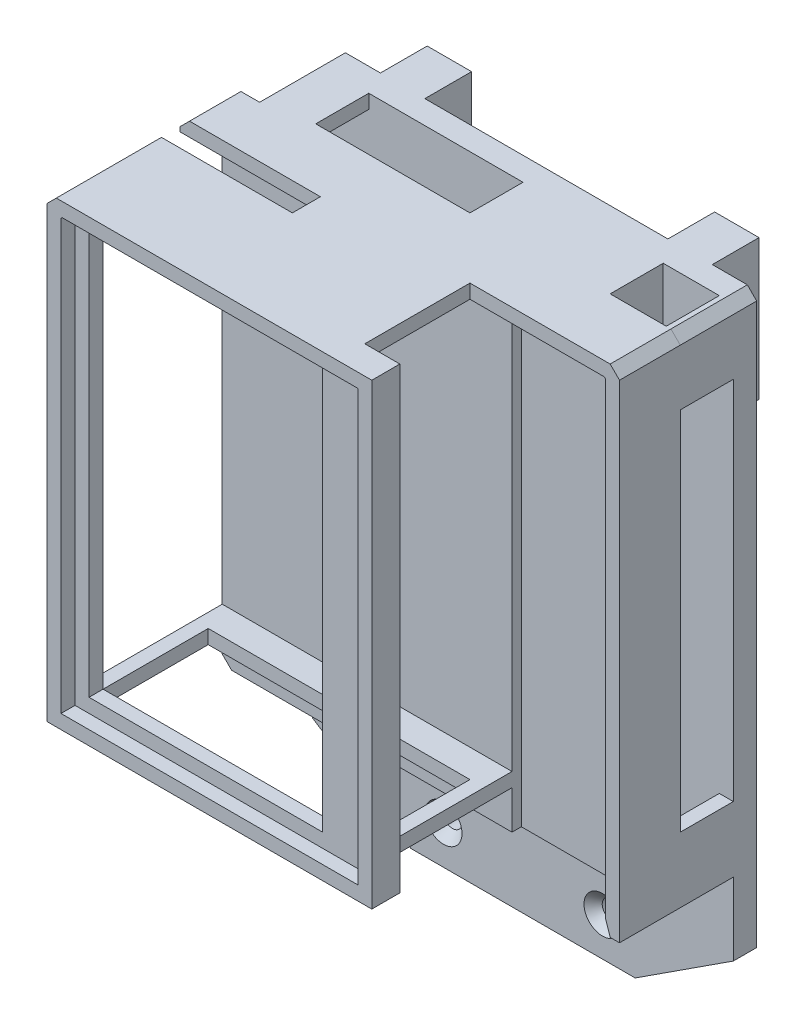
SolidWorks part; units mm, degrees
note: The reader was unsure of these and kept them because the rebuilt part matched: shared geometry of "Sketch14<2>".
ref_plane "Front Plane" through (0, 0, 0) normal (0, 0, 1) x (1, 0, 0)
ref_plane "Top Plane" through (0, 0, 0) normal (0, 1, 0) x (1, 0, 0)
ref_plane "Right Plane" through (0, 0, 0) normal (1, 0, 0) x (0, 0, -1)
sketch "Sketch2" plane through (0, 0, 0) normal (0, 0, 1) x (1, 0, 0)
  line L0 (-45, 122) -> (-45, 0.1976)
  line L1 (-24, -13.44) -> (24, -13.44)
  line L2 (45, 0.1976) -> (45, 122)
  line L3 (45, 122) -> (-45, 122)
  line L4 (-45, 0.1976) -> (-24, -13.44)
  line L5 (24, -13.44) -> (45, 0.1976)
  line L6 (52.1567, -47.9756) -> (61.3959, -41.9756) construction
  line L7 (-58.6041, -41.9756) -> (-49.3649, -47.9756) construction
  dimension "D1" = 48
  dimension "D2" = 135.44
extrude "Boss-Extrude1" add sketch "Sketch2" along normal blind 5
chamfer "Chamfer1" distance 2 2 edges at (-45, 122, 2.5) (45, 122, 2.5)
sketch "Sketch4" plane through (0, 0, 5) normal (0, 0, 1) x (1, 0, 0)
  line L0 (-45, 120) -> (-43, 122)
  line L1 (-43, 122) -> (-33, 122)
  line L2 (43, 122) -> (-43, 122) construction
  line L3 (-33, 122) -> (-33, 119)
  line L4 (-33, 119) -> (-41.7574, 119)
  line L5 (-41.7574, 119) -> (-42, 118.7574)
  line L9 (-45, 118.7574) -> (-45, 120)
  line L10 (-42, 118.7574) -> (-45, 118.7574)
  line L11 (-45, 15.7574) -> (-33, 15.7574)
  line L12 (-45, 120) -> (-45, 0.1976) construction
  line L13 (-33, 15.7574) -> (-33, 18.7574)
  line L14 (-33, 18.7574) -> (-45, 18.7574)
  line L15 (-45, 18.7574) -> (-45, 15.7574)
  line L16 (0, 122) -> (30, 122)
  line L17 (30, 122) -> (30, 108)
  line L18 (30, 108) -> (27, 108)
  line L19 (27, 108) -> (27, 119)
  line L20 (27, 119) -> (0, 119)
  line L21 (0, 119) -> (0, 122)
  line L22 (0, 15.7574) -> (30, 15.7574)
  line L23 (30, 15.7574) -> (30, 29.7574)
  line L24 (30, 29.7574) -> (27, 29.7574)
  line L25 (27, 29.7574) -> (27, 18.7574)
  line L26 (27, 18.7574) -> (0, 18.7574)
  line L27 (0, 18.7574) -> (0, 15.7574)
  dimension "D1" = 100
  dimension "D2" = 3
  dimension "D3" = 3
  dimension "D4" = 3
  dimension "D5" = 3
  dimension "D6" = 3
  dimension "D7" = 3
  dimension "D8" = 72
  dimension "D9" = 14
  dimension "D10" = 30
  dimension "D11" = 12
extrude "Boss-Extrude2" add sketch "Sketch4" along normal blind 11.35
sketch "Sketch5" plane through (0, 0, 16.35) normal (0, 0, 1) x (1, 0, 0)
  line L0 (-33, 122) -> (-43, 122) construction
  line L1 (45, 15.7574) -> (-45, 15.7574)
  line L2 (45, 15.7574) -> (45, 122)
  line L3 (45, 122) -> (-43, 122)
  line L4 (-45, 15.7574) -> (-45, 120)
  line L6 (-45, 118.7574) -> (-45, 18.7574) construction
  line L7 (-43, 122) -> (-45, 120)
  line L8 (45, 0.1976) -> (45, 120) construction
  line L9 (0, 15.7574) -> (30, 15.7574) construction
  point P1 (-45, 122)
extrude "Boss-Extrude3" add sketch "Sketch5" along normal blind 4 contours L2 L1 L4 L7 L3
sketch "Sketch6" plane through (0, 0, 5) normal (0, 0, 1) x (1, 0, 0)
  line L0 (38, 122) -> (43, 122)
  line L1 (43, 122) -> (30, 122) construction
  line L2 (43, 122) -> (45, 120)
  line L3 (45, 120) -> (45, 115)
  line L4 (45, 0.1976) -> (45, 120) construction
  line L5 (45, 115) -> (42, 115)
  line L6 (42, 115) -> (42, 118.7574)
  line L7 (42, 118.7574) -> (41.7574, 119)
  line L8 (41.7574, 119) -> (38, 119)
  line L9 (38, 119) -> (38, 122)
  line L10 (45, 15.7574) -> (39, 15.7574)
  line L11 (39, 15.7574) -> (39, 18.7574)
  line L12 (39, 18.7574) -> (42, 18.7574)
  line L13 (42, 18.7574) -> (42, 21.7574)
  line L14 (42, 21.7574) -> (45, 21.7574)
  line L15 (45, 21.7574) -> (45, 15.7574)
  line L16 (45, 15.7574) -> (-45, 15.7574) construction
  dimension "D1" = 3
  dimension "D2" = 3
  dimension "D3" = 3
  dimension "D4" = 5
  dimension "D5" = 5
  dimension "D6" = 3
  dimension "D7" = 3
  dimension "D8" = 6
  dimension "D9" = 6
extrude "Boss-Extrude4" add sketch "Sketch6" along normal up to surface (11.35 mm away) up to face at (0.5565, 73.4131, 16.35)
chamfer "Chamfer2" distance 2 1 edges at (45, 122, 18.35)
sketch "Sketch8" plane through (0, 0, 20.35) normal (0, 0, 1) x (1, 0, 0)
  line L0 (-37, 15.7574) -> (-37, 122)
  line L1 (45, 15.7574) -> (-45, 15.7574) construction
  line L2 (43, 122) -> (-43, 122) construction
  line L3 (-37, 122) -> (-43, 122)
  line L4 (-43, 122) -> (-45, 120)
  line L5 (-45, 120) -> (-45, 15.7574)
  line L6 (-45, 15.7574) -> (-37, 15.7574)
  line M8 (43, 122) -> (-43, 122)
  line M9 (-43, 122) -> (-45, 120)
  line M10 (-45, 120) -> (-45, 15.7574)
  line M11 (-45, 15.7574) -> (45, 15.7574)
  dimension "D1" = 8
extrude "Cut-Extrude2" cut sketch "Sketch8" against normal blind 2 contours L0 M11 M8 M9 M10
sketch "Sketch9" plane through (0, 0, 20.35) normal (0, 0, 1) x (1, 0, 0)
  line L0 (-37, 18.7574) -> (42, 18.7574)
  line L1 (42, 18.7574) -> (42, 118.7574)
  line L2 (42, 118.7574) -> (41.7574, 119)
  line L3 (41.7574, 119) -> (-37, 119)
  line L4 (-37, 18.7574) -> (-37, 15.7574)
  line L5 (43, 122) -> (-37, 122)
  line L6 (-37, 122) -> (-37, 15.7574)
  line L7 (-37, 15.7574) -> (45, 15.7574)
  line L8 (45, 15.7574) -> (45, 120)
  line L9 (45, 120) -> (43, 122)
  line L10 (43, 122) -> (-37, 122)
  line L12 (-37, 15.7574) -> (45, 15.7574)
  line L13 (45, 15.7574) -> (45, 120)
  line L14 (45, 120) -> (43, 122)
  line L15 (-37, 122) -> (-37, 119)
  dimension "D1" = 0
  dimension "D2" = 3
extrude "Boss-Extrude5" add sketch "Sketch9" along normal blind 9 contours L10 L15 L3 L2 L1 L0 L4 L12 L13 L14
sketch "Sketch10" plane through (-37, 0, 0) normal (-1, 0, 0) x (0, 0, 1)
  line L8 (18.35, 15.7574) -> (29.35, 15.7574)
  line L9 (29.35, 15.7574) -> (29.35, 18.7574)
  line L10 (29.35, 18.7574) -> (20.35, 18.7574)
  line L11 (20.35, 18.7574) -> (20.35, 119)
  line L12 (20.35, 119) -> (29.35, 119)
  line L13 (29.35, 119) -> (29.35, 122)
  line L14 (29.35, 122) -> (18.35, 122)
  line L15 (18.35, 122) -> (18.35, 15.7574)
  line L16 (18.35, 15.7574) -> (29.35, 15.7574)
  line L17 (29.35, 15.7574) -> (29.35, 18.7574)
  line L18 (29.35, 18.7574) -> (20.35, 18.7574)
  line L19 (20.35, 18.7574) -> (20.35, 119)
  line L20 (20.35, 119) -> (29.35, 119)
  line L21 (29.35, 119) -> (29.35, 122)
  line L22 (29.35, 122) -> (18.35, 122)
  line L23 (18.35, 122) -> (18.35, 15.7574)
  dimension "D1" = 0
extrude "Boss-Extrude6" add sketch "Sketch10" along normal blind 12
sketch "Sketch11" plane through (0, 0, 20.35) normal (0, 0, 1) x (1, 0, 0)
  line L0 (-49, 18.7574) -> (-49, 119)
  line L1 (-49, 119) -> (-46, 119)
  line L2 (41.7574, 119) -> (-49, 119) construction
  line L3 (-46, 119) -> (-46, 18.7574)
  line L4 (-49, 18.7574) -> (42, 18.7574) construction
  line L5 (-46, 18.7574) -> (-49, 18.7574)
  dimension "D1" = 3
extrude "Boss-Extrude7" add sketch "Sketch11" along normal up to surface (9 mm away) up to face at (6.2757, 78.9787, 29.35)
chamfer "Chamfer3" distance 2 2 edges at (-49, 15.7574, 23.85) (-49, 122, 23.85)
sketch "Sketch12" plane through (0, 18.7574, 0) normal (0, 1, 0) x (1, 0, 0)
  line L0 (-46, -20.35) -> (42, -20.35) construction
  line L1 (38, -25.35) -> (17, -25.35)
  line L2 (38, -25.35) -> (38, -20.35)
  line L3 (38, -20.35) -> (17, -20.35)
  line L4 (17, -25.35) -> (17, -20.35)
  dimension "D1" = 21
  dimension "D2" = 4
extrude "Cut-Extrude3" cut sketch "Sketch12" against normal blind 9
chamfer "Chamfer5" distance 2.33 angle 65 2 edges at (38, 18.7574, 22.85) (17, 18.7574, 22.85)
sketch "Sketch13" plane through (0, 122, 0) normal (0, 1, 0) x (1, 0, 0)
  line L1 (30, -16.35) -> (42, -16.35)
  line L2 (30, -16.35) -> (30, -5)
  line L3 (30, -5) -> (42, -5)
  line L4 (42, -16.35) -> (42, -5)
extrude "Cut-Extrude4" cut sketch "Sketch13" against normal blind 117
sketch "Sketch14" plane through (0, 115, 0) normal (0, -1, 0) x (1, 0, 0)
  line L4 (45, 5) -> (45, 16.35)
  line L5 (45, 16.35) -> (42, 16.35)
  line L6 (42, 16.35) -> (42, 5)
  line L7 (42, 5) -> (45, 5)
  line L8 (45, 5) -> (45, 16.35)
  line L9 (45, 16.35) -> (42, 16.35)
  line L10 (42, 16.35) -> (42, 5)
  line L11 (42, 5) -> (45, 5)
  dimension "D1" = 0
extrude "Boss-Extrude8" add sketch "Sketch14" along normal up to surface (7 mm away) up to face at (28.5, 108, 10.675)
extrude "Boss-Extrude9" add sketch "Sketch14<2>" along normal up to surface (8 mm away) from surface
sketch "Sketch14<2>" plane through (0, 115, 0) normal (0, -1, 0) x (1, 0, 0) same geometry as "Sketch14"
sketch "Sketch15" plane through (-49, 0, 0) normal (-1, 0, 0) x (0, 0, 1)
  line L0 (29.35, 17.7574) -> (29.35, 120) construction
  line L1 (29.35, 119) -> (20.35, 119)
  line L2 (29.35, 119) -> (29.35, 27)
  line L3 (29.35, 27) -> (20.35, 27)
  line L4 (20.35, 119) -> (20.35, 27)
  line L6 (20.35, 18.7574) -> (20.35, 119) construction
  dimension "D1" = 92
extrude "Cut-Extrude5" cut sketch "Sketch15" against normal blind 10
sketch "Sketch16" plane through (0, 0, 29.35) normal (0, 0, 1) x (1, 0, 0)
  line L0 (13, 122) -> (13, 119)
  line L1 (-49, 27) -> (13, 27)
  line L2 (13, 27) -> (13, 24)
  line L3 (13, 24) -> (-49, 24)
  line L5 (-49, 24) -> (-49, 27)
  line L6 (-46, 27) -> (-49, 27) construction
  line L7 (-49, 17.7574) -> (-49, 27) construction
  line L14 (-46, 27) -> (-49, 27)
  line L15 (-49, 27) -> (-49, 17.7574)
  line L16 (-49, 17.7574) -> (-47, 15.7574)
  line L17 (-47, 15.7574) -> (45, 15.7574)
  line L18 (45, 15.7574) -> (45, 120)
  line L19 (45, 120) -> (43, 122)
  line L20 (43, 122) -> (-47, 122)
  line L21 (-47, 122) -> (-49, 120)
  line L22 (-49, 120) -> (-49, 119)
  line L23 (-49, 119) -> (41.7574, 119)
  line L24 (41.7574, 119) -> (42, 118.7574)
  line L25 (42, 118.7574) -> (42, 18.7574)
  line L26 (42, 18.7574) -> (-46, 18.7574)
  line L27 (-46, 18.7574) -> (-46, 27)
  line L34 (13, 122) -> (-47, 122)
  line L35 (-47, 122) -> (-49, 120)
  line L36 (-49, 120) -> (-49, 119)
  line L37 (-49, 119) -> (13, 119)
  dimension "D2" = 62
  dimension "D3" = 3
  dimension "D1" = 0
extrude "Boss-Extrude10" add sketch "Sketch16" along normal blind 31.5 from surface at -9 starting at face at (4.8134, 44.2445, 20.35)
sketch "Sketch17" plane through (0, 0, 51.85) normal (0, 0, 1) x (1, 0, 0)
  line L0 (-49, 119) -> (-49, 27)
  line L1 (13, 27) -> (13, 119)
  line L4 (-49, 24) -> (13, 24)
  line L5 (-47, 122) -> (-49, 120)
  line L6 (-49, 120) -> (-49, 119)
  line L7 (-49, 119) -> (13, 119)
  line L8 (13, 119) -> (13, 122)
  line L9 (13, 122) -> (-47, 122)
  line L10 (-47, 122) -> (-49, 120)
  line L11 (-49, 120) -> (-49, 119)
  line L13 (13, 119) -> (13, 122)
  line L14 (13, 122) -> (-47, 122)
  line L15 (13, 24) -> (13, 27)
  line L16 (13, 27) -> (-49, 27)
  line L17 (-49, 27) -> (-49, 24)
  line L18 (-49, 24) -> (13, 24)
  line L19 (13, 24) -> (13, 27)
  line L21 (-49, 27) -> (-49, 24)
  dimension "D1" = 0
  dimension "D2" = 0
extrude "Boss-Extrude12" add sketch "Sketch17" along normal blind 6
sketch "Sketch18" plane through (0, 0, 57.85) normal (0, 0, 1) x (1, 0, 0)
  line L10 (7, 116) -> (-43, 116)
  line L11 (-43, 116) -> (-43, 30)
  line L12 (-43, 30) -> (7, 30)
  line L13 (7, 30) -> (7, 116)
  line L14 (7, 116) -> (-43, 116)
  line L15 (-43, 116) -> (-43, 30)
  line L16 (-43, 30) -> (7, 30)
  line L17 (7, 30) -> (7, 116)
  dimension "D1" = 6
extrude "Cut-Extrude6" cut sketch "Sketch18" against normal blind 6
sketch "Sketch19" plane through (0, 0, 57.85) normal (0, 0, 1) x (1, 0, 0)
  line L10 (10, 119) -> (-45.7574, 119)
  line L11 (-45.7574, 119) -> (-46, 118.7574)
  line L12 (-46, 118.7574) -> (-46, 27)
  line L13 (-46, 27) -> (10, 27)
  line L14 (10, 27) -> (10, 119)
  line L15 (10, 119) -> (-45.7574, 119)
  line L16 (-45.7574, 119) -> (-46, 118.7574)
  line L17 (-46, 118.7574) -> (-46, 27)
  line L18 (-46, 27) -> (10, 27)
  line L19 (10, 27) -> (10, 119)
  dimension "D1" = 3
extrude "Cut-Extrude7" cut sketch "Sketch19" against normal blind 3
sketch "Sketch20" plane through (13, 0, 0) normal (1, 0, 0) x (0, 0, -1)
  line L0 (-57.85, 122) -> (-29.35, 122) construction
  line L1 (-57.85, 24) -> (-51.85, 24)
  line L2 (-57.85, 24) -> (-57.85, 122)
  line L3 (-57.85, 122) -> (-51.85, 122)
  line L4 (-51.85, 24) -> (-51.85, 122)
extrude "Cut-Extrude8" cut sketch "Sketch20" against normal blind 3
sketch "Sketch21" plane through (10, 0, 0) normal (1, 0, 0) x (0, 0, -1)
  line L10 (-57.85, 27) -> (-57.85, 24)
  line L11 (-57.85, 24) -> (-51.85, 24)
  line L12 (-51.85, 24) -> (-51.85, 27)
  line L13 (-51.85, 27) -> (-51.85, 119)
  line L14 (-51.85, 119) -> (-51.85, 122)
  line L15 (-51.85, 122) -> (-57.85, 122)
  line L16 (-57.85, 122) -> (-57.85, 119)
  line L17 (-57.85, 119) -> (-54.85, 119)
  line L18 (-54.85, 119) -> (-54.85, 27)
  line L19 (-54.85, 27) -> (-57.85, 27)
  line L20 (-57.85, 27) -> (-57.85, 24)
  line L21 (-57.85, 24) -> (-51.85, 24)
  line L22 (-51.85, 24) -> (-51.85, 27)
  line L23 (-51.85, 27) -> (-51.85, 119)
  line L24 (-51.85, 119) -> (-51.85, 122)
  line L25 (-51.85, 122) -> (-57.85, 122)
  line L26 (-57.85, 122) -> (-57.85, 119)
  line L27 (-57.85, 119) -> (-54.85, 119)
  line L28 (-54.85, 119) -> (-54.85, 27)
  line L29 (-54.85, 27) -> (-57.85, 27)
  dimension "D1" = 0
extrude "Boss-Extrude13" add sketch "Sketch21" along normal blind 10.5
sketch "Sketch22" plane through (0, 0, 54.85) normal (0, 0, 1) x (1, 0, 0)
  line L0 (20.5, 119) -> (20.5, 27)
  line L1 (20.5, 27) -> (17.5, 27)
  line L2 (17.5, 27) -> (17.5, 119)
  line L3 (20.5, 119) -> (-45.7574, 119) construction
  line L4 (17.5, 119) -> (20.5, 119)
  line L5 (-46, 27) -> (20.5, 27) construction
  dimension "D1" = 3
extrude "Boss-Extrude14" add sketch "Sketch22" along normal blind 3
sketch "Sketch23" plane through (0, 0, 20.35) normal (0, 0, 1) x (1, 0, 0)
  line L0 (13, 15.7574) -> (13, 119)
  line L1 (13, 119) -> (41.7574, 119)
  line L2 (41.7574, 119) -> (13, 119) construction
  line L3 (41.7574, 119) -> (-49, 119) construction
  line L4 (41.7574, 119) -> (42, 118.7574)
  line L5 (42, 118.7574) -> (41.7574, 119) construction
  line L6 (42, 118.7574) -> (42, 15.7574)
  line L7 (13, 15.7574) -> (42, 15.7574)
  line L8 (38, 15.7574) -> (17, 15.7574) construction
  line L10 (42, 18.2926) -> (42, 118.7574) construction
extrude "Cut-Extrude9" cut sketch "Sketch23" along normal blind 10 from offset 2 offset against normal yes
sketch "Sketch24" plane through (0, 0, 29.35) normal (0, 0, 1) x (1, 0, 0)
  line L0 (42, 18.7574) -> (43, 15.7574)
  line L7 (-47, 15.7574) -> (45, 15.7574)
  line L8 (13, 122) -> (13, 119)
  line L9 (42, 18.7574) -> (-46, 18.7574)
  line L10 (-46, 18.7574) -> (-46, 24)
  line L11 (-46, 24) -> (-49, 24)
  line L12 (-49, 24) -> (-49, 17.7574)
  line L13 (-49, 17.7574) -> (-47, 15.7574)
  line L14 (-47, 15.7574) -> (45, 15.7574)
  line L15 (13, 122) -> (13, 119)
  line L16 (42, 18.7574) -> (-46, 18.7574)
  line L17 (-46, 18.7574) -> (-46, 24)
  line L18 (-46, 24) -> (-49, 24)
  line L19 (-49, 24) -> (-49, 17.7574)
  line L20 (-49, 17.7574) -> (-47, 15.7574)
  line L27 (13, 119) -> (41.7574, 119)
  line L28 (13, 119) -> (41.7574, 119)
  line L29 (41.7574, 119) -> (42, 118.7574)
  line L30 (41.7574, 119) -> (42, 118.7574)
  line L31 (42, 118.7574) -> (42, 18.7574)
  line L32 (42, 118.7574) -> (42, 18.7574)
  line L33 (45, 15.7574) -> (45, 120)
  line L34 (45, 15.7574) -> (45, 120)
  line L35 (45, 120) -> (43, 122)
  line L36 (45, 120) -> (43, 122)
  line L37 (43, 122) -> (13, 122)
  line L38 (43, 122) -> (13, 122)
  line M8 (-47, 15.7574) -> (45, 15.7574)
  line M10 (42, 18.7574) -> (-46, 18.7574)
  line M11 (-46, 18.7574) -> (-46, 24)
  line M12 (-46, 24) -> (-49, 24)
  line M13 (-49, 24) -> (-49, 17.7574)
  line M14 (-49, 17.7574) -> (-47, 15.7574)
  dimension "D1" = 0
extrude "Cut-Extrude10" cut sketch "Sketch24" against normal up to surface (9 mm away) contours L0 M10 M11 M12 M13 M14 M8 up to face at (-10.7993, 20.7615, 20.35)
sketch "Sketch25" plane through (0, 0, 0) normal (0, 0, -1) x (-1, 0, 0)
  line L0 (-43, 122) -> (43, 122) construction
  line L1 (35.5, 122) -> (26, 122)
  line L2 (35.5, 122) -> (35.5, 92)
  line L3 (35.5, 92) -> (26, 92)
  line L4 (26, 122) -> (26, 92)
  line L6 (-35.5, 92) -> (-26, 92)
  line L7 (-35.5, 92) -> (-35.5, 122)
  line L8 (-35.5, 122) -> (-26, 122)
  line L9 (-26, 92) -> (-26, 122)
  dimension "D1" = 9.5
extrude "Boss-Extrude15" add sketch "Sketch25" along normal up to surface (10 mm away)
hole_wizard "CSK for M4 SFHCS2" positions "Sketch28" profile "Sketch29" countersink size "M4" standard "ANSI Metric"
sketch "Sketch28" plane through (-695.683, 1385.2473, 5) normal (0, 0, 1) x (1, 0, 0)
  point P0 (678.683, -1390.4673)
  point P2 (712.683, -1390.4673)
sketch "Sketch29" plane through (-17, -5.22, 5) normal (1, 0, 0) x (0, -1, 0)
  line L0 (0, 0) -> (0, 14.2017)
  line L1 (0, 14.2017) -> (2, 13)
  line L2 (2, 13) -> (2, 1.95)
  line L3 (2, 1.95) -> (3.95, 0)
  line L4 (3.95, 0) -> (0, 0)
  line L5 (-2, 1.95) -> (-3.95, 0) construction
  line L6 (0, 14.2017) -> (-2, 13) construction
  line L7 (0, -6.35) -> (0, 107.95) construction
  dimension "Hole Dia." = 4
  dimension "Hole Depth" = 13
  dimension "Near C'Sink Dia." = 7.9
  dimension "Near C'Sink Angle" = 90
  dimension "Drill Angle" = 118
chamfer "Chamfer6" distance 2 angle 65 1 edges at (-45, 67.8787, 18.35)
extrude "Cut-Extrude11" cut sketch "Sketch30" against normal blind 18.5
sketch "Sketch30" plane through (-695.683, 24, -941.083) normal (0, -1, 0) x (1, 0, 0)
  line L2 (649.683, 992.933) -> (705.683, 992.933)
  line L3 (649.683, 992.933) -> (649.683, 967.433)
  line L4 (649.683, 967.433) -> (705.683, 967.433)
  line L5 (705.683, 992.933) -> (705.683, 967.433)
sketch "Sketch32" plane through (0, 122, 0) normal (0, 1, 0) x (1, 0, 0)
  line L0 (-49, -57.85) -> (-49, -18.35) construction
  line L1 (-19, -29.35) -> (-49, -29.35)
  line L2 (-19, -29.35) -> (-19, -35.35)
  line L3 (-19, -35.35) -> (-49, -35.35)
  line L4 (-49, -29.35) -> (-49, -35.35)
  line L5 (41.7574, -29.35) -> (13, -29.35) construction
  dimension "D1" = 6
  dimension "D2" = 30
extrude "Cut-Extrude13" cut sketch "Sketch32" against normal blind 10
hole_wizard "CSK for M4 SFHCS3" positions "Sketch33" profile "Sketch34" countersink size "M4" standard "ANSI Metric"
sketch "Sketch33" plane through (45, 1385.2473, -941.083) normal (1, 0, 0) x (0, 1, 0)
  point P0 (-1278.2473, 936.083)
sketch "Sketch34" plane through (45, 107, -5) normal (0, 1, 0) x (0, 0, -1)
  line L0 (0, 0) -> (0, 20.2017)
  line L1 (0, 20.2017) -> (2, 19)
  line L2 (2, 19) -> (2, 1.95)
  line L3 (2, 1.95) -> (3.95, 0)
  line L4 (3.95, 0) -> (0, 0)
  line L5 (-2, 1.95) -> (-3.95, 0) construction
  line L6 (0, 20.2017) -> (-2, 19) construction
  line L7 (0, -6.35) -> (0, 107.95) construction
  dimension "Hole Dia." = 4
  dimension "Hole Depth" = 19
  dimension "Near C'Sink Dia." = 7.9
  dimension "Near C'Sink Angle" = 90
  dimension "Drill Angle" = 118
hole_wizard "Ø4.0mm Dowel Hole1" positions "Sketch35" profile "Sketch37" hole size "Ø4.0" standard "ANSI Metric" end condition up to next
sketch "Sketch35" plane through (-35.5, 0, 0) normal (-1, 0, 0) x (0, 0, 1)
  point P0 (-5, 107)
sketch "Sketch37" plane through (-35.5, 107, -5) normal (0, 1, 0) x (0, 0, 1)
  line L0 (0, 0) -> (0, 9.5)
  line L1 (0, 9.5) -> (2, 9.5)
  line L2 (2, 9.5) -> (2, 0)
  line L5 (2, 0) -> (0, 0)
  line L11 (0, -6.35) -> (0, 107.95) construction
  dimension "Thru Hole Dia." = 4
  dimension "Thru Hole Depth" = 9.5
